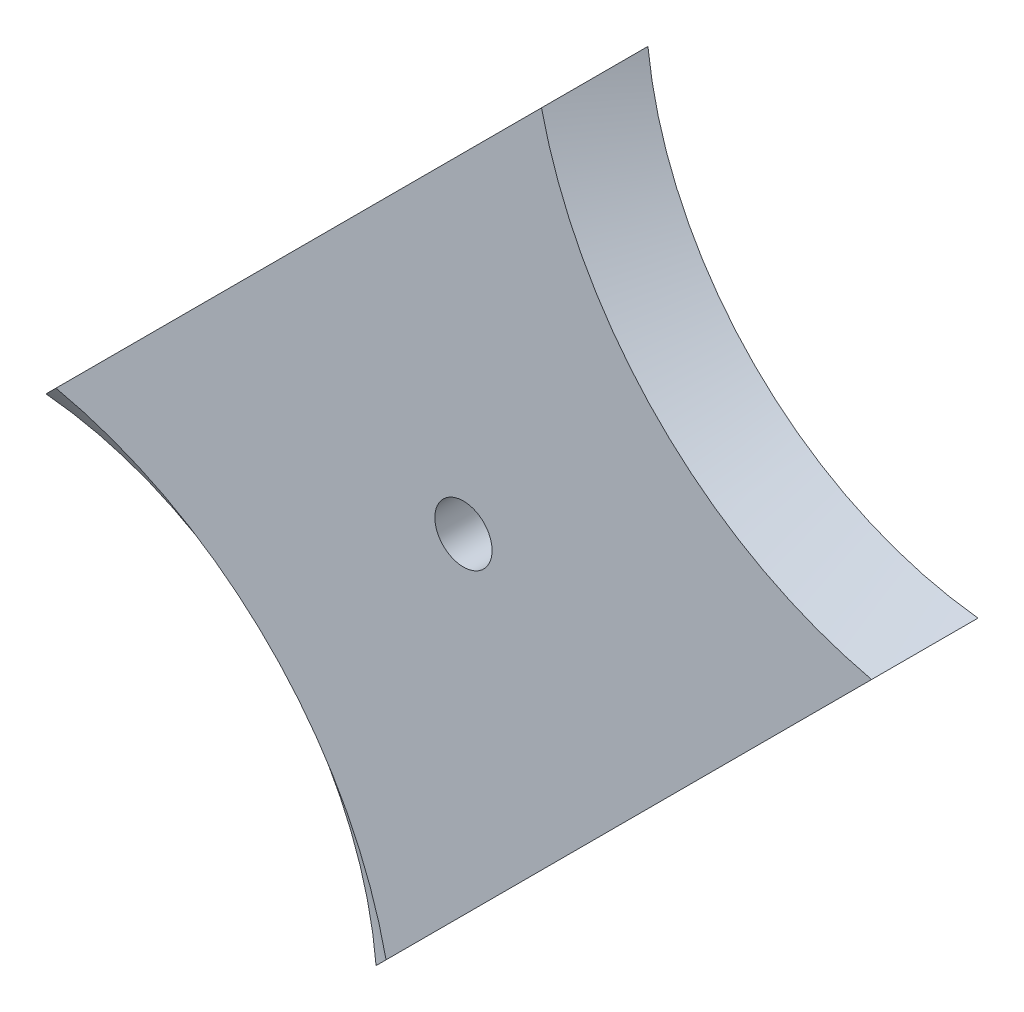
SolidWorks part; units mm, degrees
ref_plane "Front Plane" through (0, 0, 0) normal (0, 0, 1) x (1, 0, 0)
ref_plane "Top Plane" through (0, 0, 0) normal (0, 1, 0) x (1, 0, 0)
ref_plane "Right Plane" through (0, 0, 0) normal (1, 0, 0) x (0, 0, -1)
sketch "Sketch3" plane through (0, 0, 0) normal (0, 0, 1) x (1, 0, 0)
  line L9 (48.5673, 137.8283) -> (110.5673, 199.8283)
  line L10 (110.5673, 199.8283) -> (144.5673, 165.8283) construction
  line L11 (144.5673, 165.8283) -> (82.5673, 103.8283)
  line L12 (82.5673, 103.8283) -> (48.5673, 137.8283) construction
  line L13 (65.5673, 120.8283) -> (127.5673, 182.8283) construction
  line L14 (110.5673, 199.8283) -> (121.5673, 176.8283) construction
  line L15 (121.5673, 176.8283) -> (144.5673, 165.8283) construction
  line L16 (48.5673, 137.8283) -> (71.5673, 126.8283) construction
  line L17 (71.5673, 126.8283) -> (82.5673, 103.8283) construction
  circle A0 centre (96.5673, 151.8283) radius 2.9469
  arc A1 (82.5673, 103.8283) -> (48.5673, 137.8283) centre (45.2197, 100.4807) ccw
  arc A2 (144.5673, 165.8283) -> (110.5673, 199.8283) centre (148.7243, 203.9853) cw
  dimension "D1" = 87.6812
  dimension "D2" = 48.0833
extrude "Boss-Extrude1" add sketch "Sketch3" along normal blind 5 contours L9 L16 L13 L14 | L13 L17 L11 L15 region at (80.5273, 167.8683, 0)
chamfer "Chamfer1" distance 5 angle 54 1 edges at (121.5836, 176.8446, 5) first distance on face at (124.5754, 179.8364, 2.5)
chamfer "Chamfer2" distance 5 angle 54 1 edges at (71.7343, 126.9953, 5) first distance on face at (68.6508, 123.9118, 2.5)
